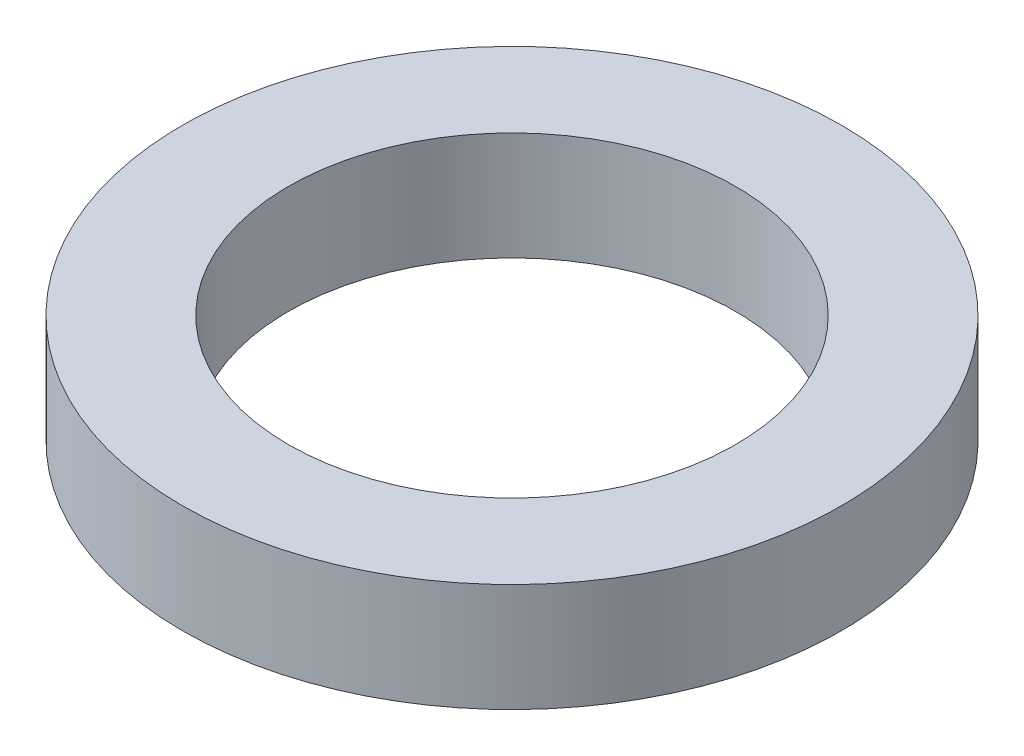
SolidWorks part; units mm, degrees
ref_plane "Front Plane" through (0, 0, 0) normal (0, 0, 1) x (1, 0, 0)
ref_plane "Top Plane" through (0, 0, 0) normal (0, 1, 0) x (1, 0, 0)
ref_plane "Right Plane" through (0, 0, 0) normal (1, 0, 0) x (0, 0, -1)
sketch "Sketch1" plane through (0, 0, 0) normal (0, 1, 0) x (1, 0, 0)
  circle A0 centre (0, 0) radius 70
  dimension "FLANGE_OD" = 140
extrude "Boss-Extrude1" add sketch "Sketch1" along normal blind 23
sketch "Sketch2" plane through (0, 0, 0) normal (0, 1, 0) x (1, 0, 0)
  circle A0 centre (0, 0) radius 47.5
  dimension "BORE_D" = 95
extrude "Cut-Extrude1" cut sketch "Sketch2" along normal through all
sketch "Sketch3" plane through (0, 23, 0) normal (0, 1, 0) x (1, 0, 0)
  circle A0 centre (0, 0) radius 28.171 construction
  circle A1 centre (-28.171, 0) radius 1.7367
  dimension "BOLT_D" = 3.4735
  dimension "BOLT_PCD" = 56.342
extrude "Cut-Extrude2" cut sketch "Sketch3" against normal blind 15.6824 rebuild error yes
pattern_circular "CirPattern1" count 3 over 360 rebuild error yes
